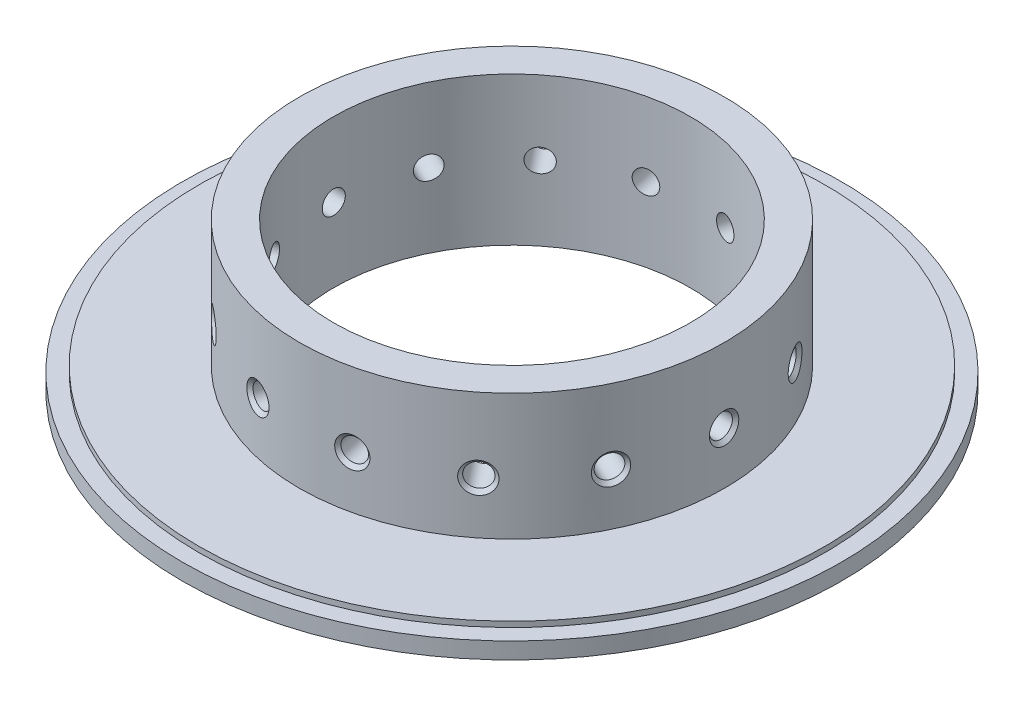
SolidWorks part; units mm, degrees
material "6061-T6 (SS)"
ref_plane "Front Plane" through (0, 0, 0) normal (0, 0, 1) x (1, 0, 0)
ref_plane "Top Plane" through (0, 0, 0) normal (0, 1, 0) x (1, 0, 0)
ref_plane "Right Plane" through (0, 0, 0) normal (1, 0, 0) x (0, 0, -1)
sketch "Sketch1" plane through (0, 0, 0) normal (0, 0, 1) x (1, 0, 0)
  line L0 (0, 0) -> (0, -26301.4581) construction
  line L1 (32.5, 0) -> (60, 0)
  line L2 (60, 0) -> (60, 3)
  line L3 (60, 3) -> (57, 3)
  line L4 (57, 3) -> (57, 4)
  line L5 (57, 4) -> (38.71, 4)
  line L6 (38.71, 4) -> (38.71, 27)
  line L7 (38.71, 27) -> (32.5, 27)
  line L8 (32.5, 27) -> (32.5, 0)
  dimension "D1" = 77.42
  dimension "D2" = 65
  dimension "D3" = 120
  dimension "D4" = 114
  dimension "D5" = 3
  dimension "D6" = 1
  dimension "D7" = 23
revolve "Revolve1" add sketch "Sketch1" angle 360 about L0
hole_wizard "M5 Tapped Hole1" positions "3DSketch1" profile "Sketch2" tap size "M5" standard "ISO" end condition up to next
sketch3d "3DSketch1"
  point P0 (38.71, 13.5, 0)
  dimension "D1" = 9.5
sketch "Sketch2" plane through (38.71, 13.5, 0) normal (0, 1, 0) x (0, 0, -1)
  line L0 (0, 0) -> (0, 6.21)
  line L1 (0, 6.21) -> (2.1, 6.21)
  line L2 (2.1, 6.21) -> (2.1, 0.675)
  line L3 (2.1, 0.675) -> (2.775, 0)
  line L5 (2.775, 0) -> (0, 0)
  line L6 (-2.1, 0.675) -> (-2.775, 0) construction
  line L11 (0, -6.35) -> (0, 107.95) construction
  dimension "Thru Tap Drill Dia." = 4.2
  dimension "Thru Tap Drill Depth" = 6.21
  dimension "Near C'Sink Dia." = 5.55
  dimension "Near C'Sink Angle" = 90
cosmetic thread "Hole Thread1" parameters "D2"=5
pattern_circular "CirPattern1" count 14 over 360 about axis through (0, 0, 0) along (0, 1, 0) of "M5 Tapped Hole1" reverse direction yes
cosmetic thread "Hole Thread2" parameters "D2"=5
cosmetic thread "Hole Thread3" parameters "D2"=5
cosmetic thread "Hole Thread4" parameters "D2"=5
cosmetic thread "Hole Thread5" parameters "D2"=5
cosmetic thread "Hole Thread6" parameters "D2"=5
cosmetic thread "Hole Thread7" parameters "D2"=5
cosmetic thread "Hole Thread8" parameters "D2"=5
cosmetic thread "Hole Thread9" parameters "D2"=5
cosmetic thread "Hole Thread10" parameters "D2"=5
cosmetic thread "Hole Thread11" parameters "D2"=5
cosmetic thread "Hole Thread12" parameters "D2"=5
cosmetic thread "Hole Thread13" parameters "D2"=5
cosmetic thread "Hole Thread14" parameters "D2"=5
equation "\"CanSat_Len\"= 400mm"
equation "\"CanSat_Dia\"= 150mm"
equation "\"BodyTube_ID\"= 114mm"
equation "\"BodyTube_OD\"= 120mm"
equation "\"PayLoadBay_ID\"= 164mm"
equation "\"PayLoadBay_OD\"= 170mm"
equation "\"ParachuteBay_Pitch\"= 300mm"
equation "\"ElectronicsTray_PitchDist\"= 50mm"
equation "\"ElectronicsTray_Height\"= 140mm"
equation "\"MotorDia\"= 98mm"
equation "\"MotorLen\"=289mm"
equation "\"D3@Sketch1\"=\"BodyTube_OD\""
equation "\"D4@Sketch1\"=\"BodyTube_ID\""
